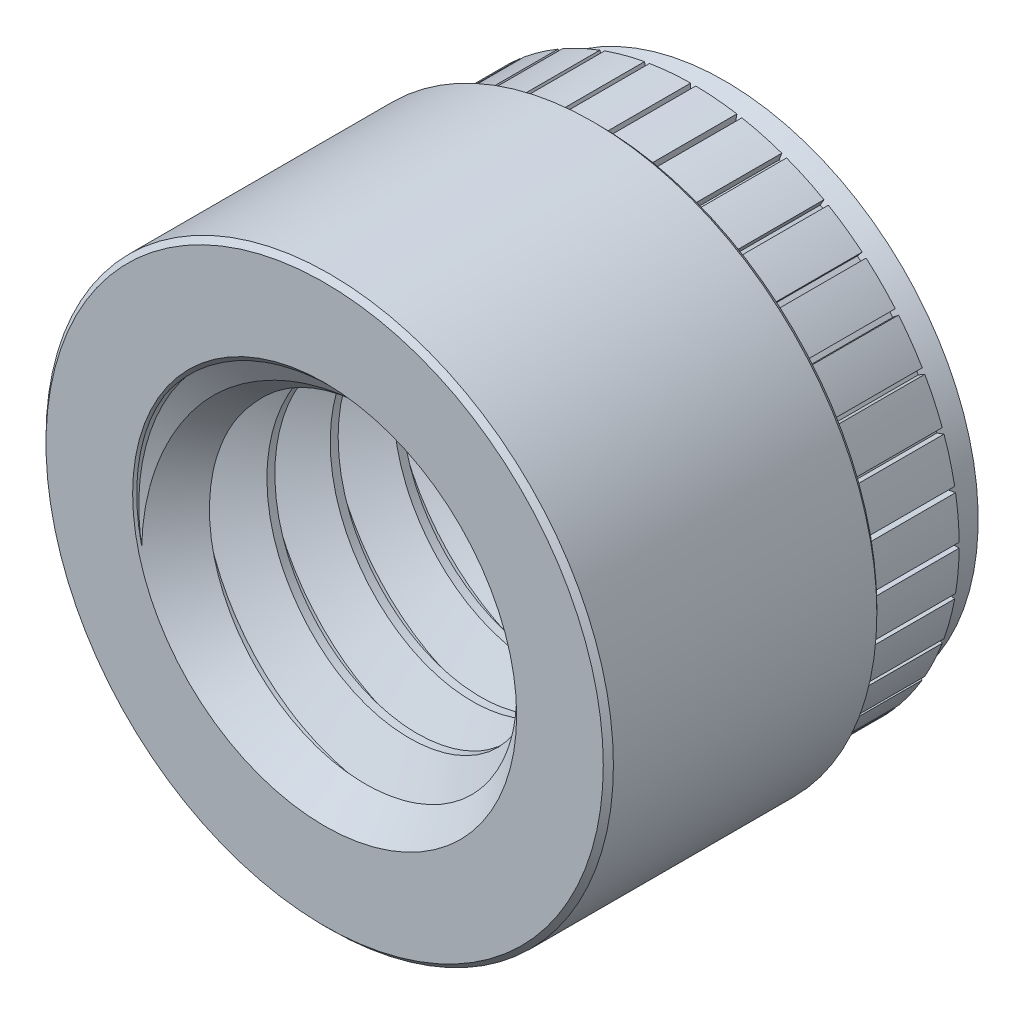
SolidWorks part; units mm, degrees
ref_plane "Front Plane" through (0, 0, 0) normal (0, 0, 1) x (1, 0, 0)
ref_plane "Top Plane" through (0, 0, 0) normal (0, 1, 0) x (1, 0, 0)
ref_plane "Right Plane" through (0, 0, 0) normal (1, 0, 0) x (0, 0, -1)
sketch "Sketch1" plane through (0, 0, 0) normal (0, 0, 1) x (1, 0, 0)
  circle A0 centre (0, 0) radius 7.112
  dimension "A" = 14.224
extrude "Extrude1" add sketch "Sketch1" against normal blind 6.858
sketch "Sketch15" plane through (0, 0, -6.858) normal (0, 0, -1) x (-1, 0, 0)
  circle A0 centre (0, 0) radius 6.35
  dimension "hole dia" = 12.7
sketch "Sketch2" plane through (0, 0, -6.858) normal (0, 0, -1) x (-1, 0, 0)
  circle A0 centre (0, 0) radius 6.6675
  dimension "D1" = 13.335
extrude "Extrude2" add sketch "Sketch2" along normal blind 3.175
sketch "Sketch3" plane through (0, 0, -10.033) normal (0, 0, -1) x (-1, 0, 0)
  line L0 (0, 6.477) -> (0, 7.112)
  circle A1 centre (0, 0) radius 7.112 construction
  circle A2 centre (0, 0) radius 6.477
  circle A3 centre (0, 0) radius 6.477 construction
  dimension "D1" = 0.1905
extrude "Cut-Extrude-Thin1" cut sketch "Sketch3" against normal up to surface (3.175 mm away) thin up to face at (7.112, 0, -6.858) thin type mid plane wall 0.127
pattern_circular "CirPattern1" count 36 over 360 about axis through (0, 0, 0) along (0, 0, 1) of "Cut-Extrude-Thin1"
sketch "Sketch5" plane through (0, 0, -10.033) normal (0, 0, -1) x (-1, 0, 0)
  circle A0 centre (0, 0) radius 7.112 construction
  circle A3 centre (0, 0) radius 6.35
  dimension "C" = 12.7
extrude "Cut-Extrude1" cut sketch "Sketch5" against normal blind 0.7937 draft 20 flip side to cut draft outward yes
chamfer "Chamfer2" distance 0.127 angle 45 2 edges at (7.112, 0, 0) (7.112, 0, -6.858)
sketch "Sketch7" plane through (0, 0, 0) normal (0, 0, 1) x (1, 0, 0)
  circle A0 centre (0, 0) radius 4.7625
  dimension "Thread Od" = 9.525
extrude "Cut-Extrude3" cut sketch "Sketch7" against normal through all
sketch "Sketch8" plane through (0, 0, -10.033) normal (0, 0, -1) x (-1, 0, 0)
  circle A0 centre (0, 0) radius 4.7625 construction
  circle A1 centre (0, 0) radius 4.7625
curve "Helix/Spiral1" pitch 1.5875 height 13.208 turns 8.32 parameters "pitch"=1.5875
sketch "Sketch9" plane through (0, 0, 0) normal (1, 0, 0) x (0, 0, -1)
  line L0 (11.4221, 4.7625) -> (10.8267, 3.7314)
  line L1 (10.8267, 3.7314) -> (10.6283, 3.7314)
  line L2 (10.6283, 3.7314) -> (10.033, 4.7625)
  line L3 (11.4221, 4.7625) -> (10.033, 4.7625)
  line L4 (10.7275, 4.7625) -> (10.7275, 3.7314) construction
  line L5 (11.1244, 4.2469) -> (10.3307, 4.2469) construction
  line L6 (10.033, -4.7625) -> (10.033, 4.7625) construction
  dimension "D1" = 60
  dimension "D2" = 0.1984
  dimension "D3" = 0.7937
sweep "Sweep1" add profiles "Sketch9" path "Helix/Spiral1"
sketch "Sketch10" plane through (0, 0, 0) normal (0, 0, 1) x (1, 0, 0)
  circle A0 centre (0, 0) radius 7.112 construction
  circle A1 centre (0, 0) radius 7.112
extrude "Cut-Extrude4" cut sketch "Sketch10" along normal through all
sketch "Sketch11" plane through (0, 0, -10.033) normal (0, 0, -1) x (-1, 0, 0)
  circle A1 centre (0, 0) radius 6.35 construction
  circle A2 centre (0, 0) radius 6.35
extrude "Cut-Extrude5" cut sketch "Sketch11" along normal through all
sketch "Sketch13" plane through (0, 0, 0) normal (0, 0, 1) x (1, 0, 0)
  circle A2 centre (0, 0) radius 4.8133
  circle A3 centre (0, 0) radius 4.8133
  dimension "D1" = 0.0508
extrude "Cut-Extrude6" cut sketch "Sketch13" against normal through all draft 45
sketch "Sketch14" plane through (0, 0, -10.033) normal (0, 0, -1) x (-1, 0, 0)
  circle A2 centre (0, 0) radius 4.8133
  circle A3 centre (0, 0) radius 4.8133
  dimension "D1" = 0.0508
extrude "Cut-Extrude7" cut sketch "Sketch14" against normal through all draft 45
equation "\"D3@Helix/Spiral1\" = \"B@Extrude1\"+\"panel min.@Extrude2\"+.125"
equation "\"D2@Sketch9\" = \"pitch@Helix/Spiral1\"*.125"
equation "\"D3@Sketch9\" = \"pitch@Helix/Spiral1\"*.50"
equation "\"D1@Sketch2\" = \"hole dia@Sketch15\"+.025"
equation "\"D1@Cut-Extrude1\" = \"panel min.@Extrude2\"*.25"
